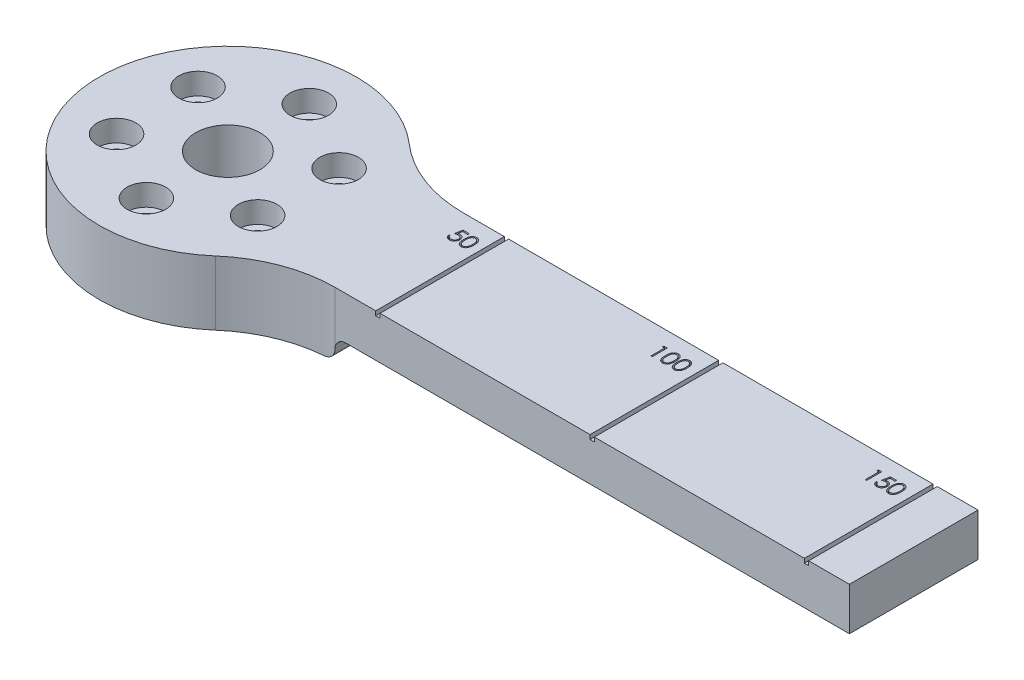
SolidWorks part; units mm, degrees
ref_plane "Front Plane" through (0, 0, 0) normal (0, 0, 1) x (1, 0, 0)
ref_plane "Top Plane" through (0, 0, 0) normal (0, 1, 0) x (1, 0, 0)
ref_plane "Right Plane" through (0, 0, 0) normal (1, 0, 0) x (0, 0, -1)
sketch "Sketch1" plane through (0, 0, 0) normal (0, 1, 0) x (1, 0, 0)
  line L2 (160, 15) -> (160, -15)
  line L3 (160, 15) -> (40, 15)
  line L4 (160, -15) -> (40, -15)
  arc A0 (19.726, 22.6027) -> (19.726, -22.6027) centre (0, 0) ccw
  circle A1 centre (0, 0) radius 7.5
  arc A2 (40, -15) -> (19.726, -22.6027) centre (40, -45.8333) ccw
  arc A3 (40, 15) -> (19.726, 22.6027) centre (40, 45.8333) cw
  point P7 (160, 0)
  dimension "D2" = 40
  dimension "D3" = 30
  dimension "D4" = 15
  dimension "D1" = 30
  dimension "D5" = 160
extrude "Boss-Extrude1" add sketch "Sketch1" along normal blind 15
sketch "Sketch2" plane through (0, 15, 0) normal (0, 1, 0) x (1, 0, 0)
  circle A0 centre (0, 0) radius 19 construction
  circle A1 centre (0, 19) radius 4.5
  circle A2 centre (16.4545, 9.5) radius 4.5
  circle A3 centre (16.4545, -9.5) radius 4.5
  circle A4 centre (0, -19) radius 4.5
  circle A5 centre (-16.4545, -9.5) radius 4.5
  circle A6 centre (-16.4545, 9.5) radius 4.5
  point P21 (0, 0)
  dimension "D1" = 38
  dimension "D2" = 9
  dimension "D3" = 6
extrude "Cut-Extrude1" cut sketch "Sketch2" against normal blind 5
sketch "Sketch3" plane through (0, 10, 0) normal (0, 1, 0) x (1, 0, 0)
  circle A0 centre (0, 19) radius 2.75
  circle A1 centre (16.4545, 9.5) radius 2.75
  circle A2 centre (16.4545, -9.5) radius 2.75
  circle A3 centre (0, -19) radius 2.75
  circle A4 centre (-16.4545, -9.5) radius 2.75
  circle A5 centre (-16.4545, 9.5) radius 2.75
  point P19 (0, 0)
  dimension "D1" = 5.5
  dimension "D2" = 6
extrude "Cut-Extrude2" cut sketch "Sketch3" against normal through all
sketch "Sketch4" plane through (0, 15, 0) normal (0, 1, 0) x (1, 0, 0)
  line L0 (49.5, 15) -> (49.5, -15)
  line L1 (160, 15) -> (40, 15) construction
  line L2 (40, -15) -> (160, -15) construction
  line L3 (50.5, 15) -> (50.5, -15)
  line L4 (99.5, 15) -> (99.5, -15)
  line L5 (100.5, 15) -> (100.5, -15)
  line L6 (149.5, 15) -> (149.5, -15)
  line L7 (150.5, 15) -> (150.5, -15)
  line L8 (49.5, 15) -> (50.5, 15)
  line L9 (49.5, -15) -> (50.5, -15)
  line L10 (99.5, 15) -> (100.5, 15)
  line L11 (99.5, -15) -> (100.5, -15)
  line L12 (149.5, 15) -> (150.5, 15)
  line L13 (149.5, -15) -> (150.5, -15)
  dimension "D1" = 1
  dimension "D2" = 49.5
  dimension "D3" = 1
  dimension "D4" = 99.5
  dimension "D5" = 1
  dimension "D6" = 149.5
extrude "Cut-Extrude3" cut sketch "Sketch4" against normal blind 1
sketch "Sketch5" plane through (0, 15, 0) normal (0, 1, 0) x (1, 0, 0)
  line L0 (49.5, 15) -> (49.5, -15) construction
  line L1 (99.5, 15) -> (99.5, -15) construction
  line L2 (149.5, 15) -> (149.5, -15) construction
  line L3 (49.5, 15) -> (40, 15) construction
  text T0 "50"
  text T1 "100"
  text T2 "150"
  dimension "D1" = 7
  dimension "D2" = 10
  dimension "D3" = 10
  dimension "D4" = 7
extrude "Cut-Extrude4" cut sketch "Sketch5" against normal blind 1
sketch "Sketch6" plane through (0, 0, 0) normal (0, 0, 1) x (1, 0, 0)
  line L0 (40, 15) -> (40, 0) construction
  line L1 (160, 0) -> (40, 0)
  line L2 (160, 0) -> (160, 5)
  line L3 (160, 5) -> (40, 5)
  line L4 (40, 0) -> (40, 5)
  dimension "D1" = 5
extrude "Cut-Extrude5" cut sketch "Sketch6" along normal mid plane 30
fillet "Fillet1" radius 2.5 2 edges at (40, 5, 0) (40, 0, 0)
